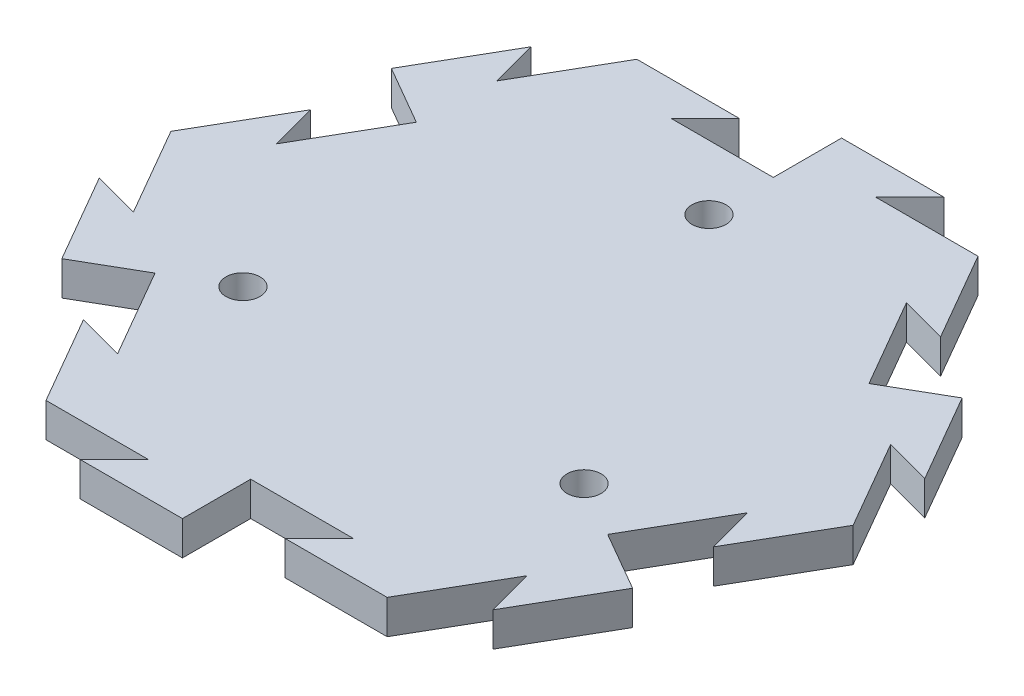
SolidWorks part; units mm, degrees
material "Cedar"
ref_plane "Front Plane" through (0, 0, 0) normal (0, 0, 1) x (1, 0, 0)
ref_plane "Top Plane" through (0, 0, 0) normal (0, 1, 0) x (1, 0, 0)
ref_plane "Right Plane" through (0, 0, 0) normal (1, 0, 0) x (0, 0, -1)
sketch "Sketch1" plane through (0, 0, 0) normal (0, 1, 0) x (1, 0, 0)
  line L0 (0, 0) -> (63.5, 0) construction
  line L1 (63.5, 0) -> (31.75, 54.9926)
  line L2 (31.75, 54.9926) -> (-31.75, 54.9926)
  line L3 (-31.75, 54.9926) -> (-63.5, 0)
  line L4 (-63.5, 0) -> (-31.75, -54.9926)
  line L5 (-31.75, -54.9926) -> (31.75, -54.9926)
  line L6 (31.75, -54.9926) -> (63.5, 0)
  circle A0 centre (0, 0) radius 54.9926 construction
  dimension "D1" = 63.5
extrude "Boss-Extrude1" add sketch "Sketch1" against normal blind 6.35
sketch "Sketch2" plane through (0, 0, 0) normal (0, 1, 0) x (1, 0, 0)
  point P1 (0, 0)
ref_axis "Axis1" through (0, 0, 0) along (0, 1, 0)
sketch "Sketch9" plane through (0, 0, 0) normal (0, 1, 0) x (1, 0, 0)
  line L1 (31.75, -18.3309) -> (0, 36.6617) construction
  line L2 (0, 36.6617) -> (-31.75, -18.3309) construction
  line L3 (-31.75, -18.3309) -> (31.75, -18.3309) construction
  circle A0 centre (0, 0) radius 18.3309 construction
  circle A1 centre (-31.75, -18.3309) radius 3.175
  dimension "D2" = 6.35
  dimension "D1" = 63.5
extrude "Cut-Extrude3" cut sketch "Sketch9" against normal through all
pattern_circular "CirPattern6" count 3 over 360 about axis through (0, 0, 0) along (0, 1, 0) of "Cut-Extrude3"
sketch "Sketch10" plane through (0, 0, 0) normal (0, 1, 0) x (1, 0, 0)
  line L0 (31.75, 54.9926) -> (41.275, 38.4948) construction
  line L1 (41.275, 38.4948) -> (32.6007, 40.8191)
  line L2 (32.6007, 40.8191) -> (42.1257, 24.3213)
  line L3 (42.1257, 24.3213) -> (47.625, 27.4963)
  line L4 (41.275, 38.4948) -> (47.625, 27.4963)
  line L5 (63.5, 0) -> (31.75, 54.9926) construction
  dimension "D1" = 45
  dimension "D2" = 6.35
extrude "Cut-Extrude4" cut sketch "Sketch10" against normal through all
sketch "Sketch11" plane through (0, 0, 0) normal (0, 1, 0) x (1, 0, 0)
  line L0 (47.625, 27.4963) -> (63.5, 0) construction
  line L1 (47.625, 27.4963) -> (53.1243, 30.6713)
  line L2 (53.1243, 30.6713) -> (62.6493, 14.1735)
  line L3 (62.6493, 14.1735) -> (53.975, 16.4978)
  line L4 (53.975, 16.4978) -> (47.625, 27.4963)
  line L5 (53.975, 16.4978) -> (63.5, 0) construction
  line L6 (53.975, 16.4978) -> (63.5, 0) construction
  line L7 (63.5, 0) -> (47.625, 27.4963) construction
  line L8 (31.75, -54.9926) -> (63.5, 0) construction
  dimension "D1" = 45
  dimension "D2" = 6.35
extrude "Boss-Extrude4" add sketch "Sketch11" against normal blind 6.35
pattern_circular "CirPattern7" count 6 over 360 about axis through (0, 0, 0) along (0, 1, 0) of "Cut-Extrude4", "Boss-Extrude4"
